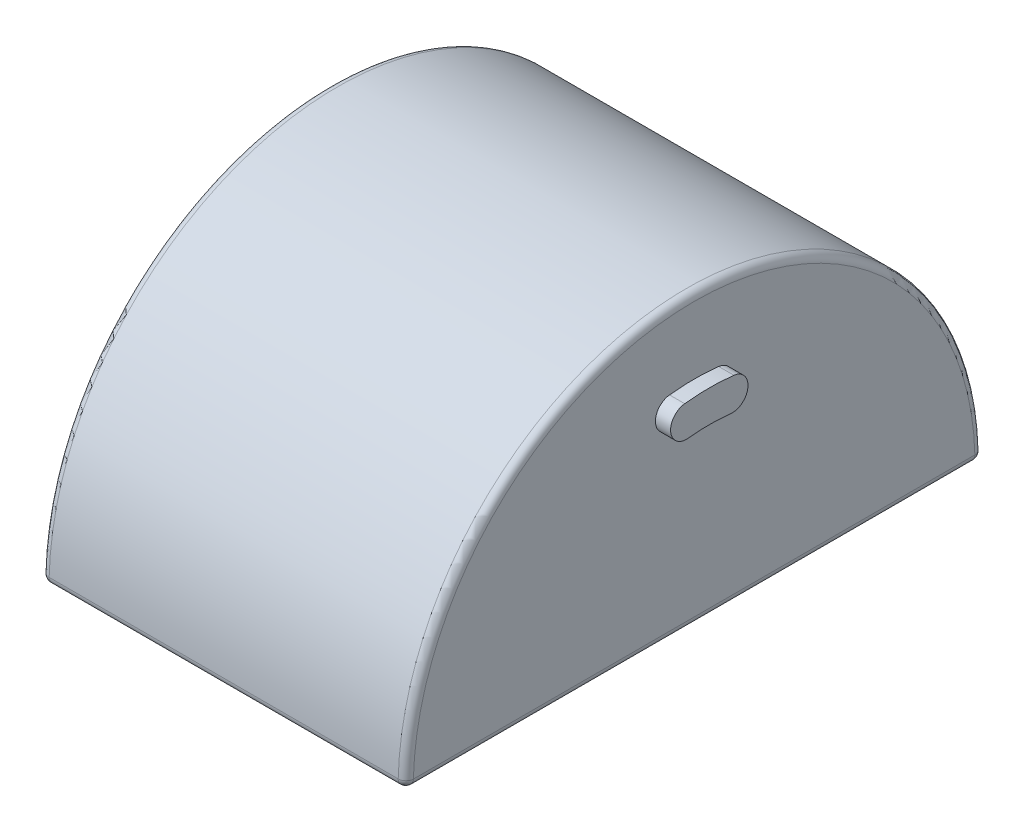
SolidWorks part; units mm, degrees
ref_plane "Front Plane" through (0, 0, 0) normal (0, 0, 1) x (1, 0, 0)
ref_plane "Top Plane" through (0, 0, 0) normal (0, 1, 0) x (1, 0, 0)
ref_plane "Right Plane" through (0, 0, 0) normal (1, 0, 0) x (0, 0, -1)
sketch "Sketch5" plane through (0, 0, 0) normal (0, 0, 1) x (1, 0, 0)
  line L0 (-13.97, 0) -> (13.97, 0)
  arc A0 (11.176, 0) -> (-11.176, 0) centre (0, 0) ccw
  arc A1 (12.7, 0) -> (-12.7, 0) centre (0, 0) ccw
  arc A2 (13.97, 0) -> (-13.97, 0) centre (0, 0) ccw
  arc A3 (12.446, 0) -> (-12.446, 0) centre (0, 0) ccw
  arc A4 (8.636, 0) -> (-8.636, 0) centre (0, 0) ccw
  dimension "D1" = 24.892
  dimension "D2" = 25.4
  dimension "D3" = 27.94
  dimension "D4" = 22.352
  dimension "D5" = 17.272
sketch "Sketch6" plane through (0, 0, 0) normal (1, 0, 0) x (0, 0, -1)
  line L0 (0, 16.5466) -> (1.905, 16.5466)
  line L1 (0, 16.5466) -> (-1.905, 16.5466)
  line L2 (0, 15.2131) -> (0, 0) construction
  line L3 (-24.1384, 0) -> (24.3191, 0)
  line L8 (24.3191, 0) -> (-24.3191, 0) construction
  arc A1 (24.1384, 0) -> (-24.1384, 0) centre (0, 0) ccw
  arc A5 (18.1341, 0) -> (-18.1341, 0) centre (0, 0) ccw
  arc A6 (14.9591, 0) -> (-14.9591, 0) centre (0, 0) ccw
  arc A7 (17.8801, 0) -> (-17.8801, 0) centre (0, 0) ccw construction
  arc A8 (15.2131, 0) -> (-15.2131, 0) centre (0, 0) ccw construction
  circle A11 centre (0, 0) radius 16.5466 construction
  arc A12 (-1.905, 16.4366) -> (1.905, 16.4366) centre (0, 0) cw construction
  arc A22 (2.0585, 17.7612) -> (-2.0585, 17.7612) centre (0, 0) ccw
  arc A23 (1.7515, 15.1119) -> (-1.7515, 15.1119) centre (0, 0) ccw
  arc A24 (1.7515, 15.1119) -> (2.0585, 17.7612) centre (1.905, 16.4366) ccw
  arc A25 (-2.0585, 17.7612) -> (-1.7515, 15.1119) centre (-1.905, 16.4366) ccw
  point P24 (0, 16.5466)
  point P25 (0, 20.0109)
  dimension "D1" = 36.2682
  dimension "D2" = 29.9182
  dimension "D8" = 33.0932
  dimension "D7" = 15.2131
  dimension "D3" = 1.905
  dimension "D6" = 1.905
  dimension "D4" = 0.254
  dimension "D5" = 0.254
extrude "Main Body Extrude" add sketch "Sketch6" along normal mid plane 30.48 contours L8 A5 A7 | L8 A6 | L8 A8 A6 | L8 A7 A8 | L8 A1 A5 | A7 L3 A8 | A8 L3 A7 | A23 region at (0, 23.5986, 0) region at (0, 18.0936, 0) region at (0, 6.3488, 0)
extrude "Inner Hinge Cut" cut sketch "Sketch5<16>" against normal mid plane 30.48 contours L0 A2 A1 | L0 A3 A0 | A4 L0 A0 | L0 A4 | A3 L0 A1 region at (0, 13.6576, 0) region at (0, 12.6716, 0) region at (0, 12.1677, 0) region at (0, 10.9261, 0) region at (0, 3.6652, 0)
sketch "Sketch5<16>" plane through (0, 0, 0) normal (0, 0, 1) x (1, 0, 0) same geometry as "Sketch5"
extrude "Groove Cut" cut sketch "Sketch5" against normal mid plane 33.02 contours A4 L0 A0 region at (0, 10.9261, 0)
extrude "Slot 1 Extrude" add sketch "Sketch6<5>" along normal blind 1.27 from surface contours A22 A25 A23 A24 region at (0, 16.4839, 0) starting at face at (15.24, 16.4148, 0)
sketch "Sketch6<5>" plane through (0, 0, 0) normal (1, 0, 0) x (0, 0, -1) same geometry as "Sketch6"
extrude "Slot 2 Extrude" add sketch "Sketch6<6>" against normal blind 1.27 from surface contours L8 A7 A8 | A22 A25 A23 A24 region at (0, 16.4839, 0) starting at face at (-15.24, 16.4148, 0)
sketch "Sketch6<6>" plane through (0, 0, 0) normal (1, 0, 0) x (0, 0, -1) same geometry as "Sketch6"
fillet "Fillet1" radius 0.635 6 edges at (0, 0, -24.1384) (-15.24, 24.1384, 0) (-15.24, 0, 0) (15.24, 24.1384, 0) (15.24, 0, 0) (0, 0, 24.1384)
equation "\"InnerBaseDiameter\"=0.98"
equation "\"D1@Sketch5\"=\"InnerBaseDiameter\""
equation "\"InnerBaseOuterGroove\"= \"InnerBaseDiameter\" - 0.1"
equation "\"InnerHingeInnerCurve\"= 1"
equation "\"InnerHingeOuterCurve\"= \"InnerHingeInnerCurve\" + 0.1"
equation "\"InnerBaseInnerGroove\"= \"InnerBaseOuterGroove\" - 0.2"
equation "\"InnerHingeWidth\"= 1.45"
equation "\"OuterBaseInnerGroove\"= \"OuterBaseOuterGroove\" - 0.25"
equation "\"OuterBaseDiameter\"= ( ( \"InnerHingeOuterCurve\" / 2 ) ^ 2 + ( \"InnerHingeLength\" / 2 ) ^ 2 ) ^ 0.5 * 2"
equation "\"InnerHingeLength\"=1.2"
equation "\"OuterBaseOuterGroove\"= \"OuterBaseDiameter\" - 0.2"
equation "\"D1@Sketch6\"=\"OuterBaseOuterGroove\""
equation "\"D2@Sketch6\"=\"OuterBaseInnerGroove\""
equation "\"D1@Main Body Extrude\" = \"InnerHingeOuterCurve\" + 0.1"
equation "\"D4@Sketch5\"=\"InnerBaseOuterGroove\""
equation "\"D5@Sketch5\"=\"InnerBaseInnerGroove\""
equation "\"D8@Sketch6\"=\"OuterBaseInnerGroove\" * 0.5 + \"OuterBaseOuterGroove\"*0.5"
equation "\"D7@Sketch6\"=\"OuterBaseInnerGroove\" * 0.5+0.01"
